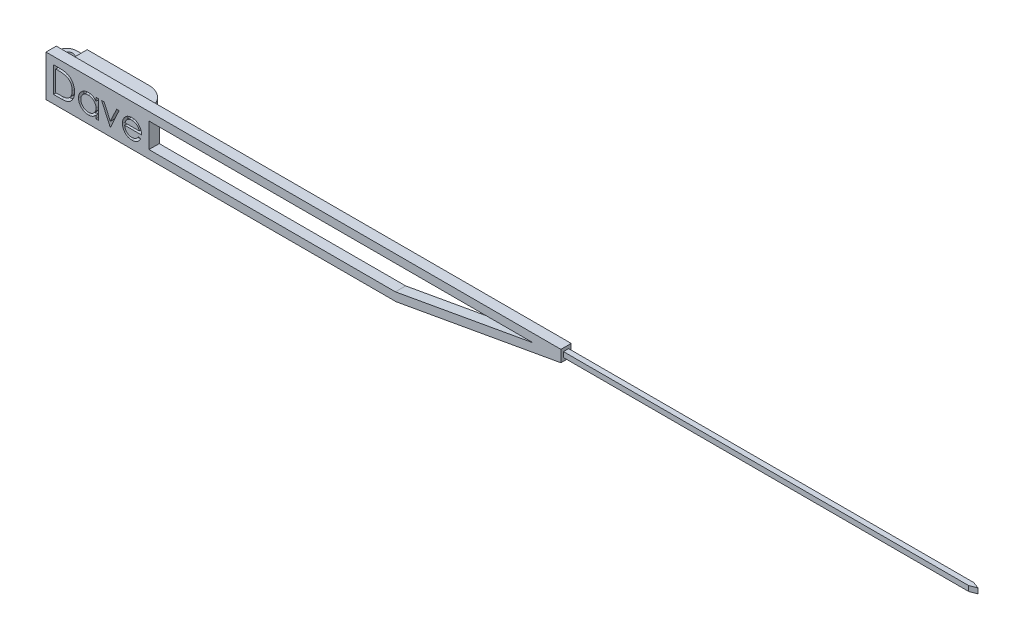
SolidWorks part; units mm, degrees
material "1060 Alloy"
ref_plane "Front" through (0, 0, 0) normal (0, 0, 1) x (1, 0, 0)
ref_plane "Top" through (0, 0, 0) normal (0, 1, 0) x (1, 0, 0)
ref_plane "Right" through (0, 0, 0) normal (1, 0, 0) x (0, 0, -1)
sketch "Sketch1" plane through (0, 0, 0) normal (0, 0, 1) x (1, 0, 0)
  line L0 (0, -2.54) -> (0, 2.54)
  line L1 (0, 2.54) -> (63.5, 2.54)
  line L2 (63.5, 2.54) -> (63.5, 1.101)
  line L3 (63.5, 1.101) -> (43.18, -2.54)
  line L4 (43.18, -2.54) -> (0, -2.54)
  point P2 (0, 0)
  dimension "D1" = 5.08
  dimension "D2" = 63.5
  dimension "D3" = 43.18
  dimension "D4" = 10.159
extrude "Boss-Extrude1" add sketch "Sketch1" along normal mid plane 1.27
sketch "Sketch3" plane through (0, 0, 0) normal (0, 0, 1) x (1, 0, 0)
  line L0 (63.5, 1.8205) -> (114.3, 1.8205)
  line L2 (63.5, 1.101) -> (63.5, 2.54) construction
  dimension "D2" = 50.8
ref_plane "Plane1" through (63.5, 0, 0) normal (1, 0, 0) x (0, 0, -1)
sketch "Sketch4" plane through (63.5, 0, 0) normal (1, 0, 0) x (0, 0, -1)
  line L0 (-0.635, 2.54) -> (0.635, 1.101) construction
  line L5 (-0.3175, 2.138) -> (0.3175, 1.503) construction
  line L6 (-0.635, 1.101) -> (0.635, 2.54) construction
  line L7 (-0.3175, 1.503) -> (0.3175, 1.503)
  line L8 (-0.3175, 1.503) -> (-0.3175, 2.138)
  line L9 (-0.3175, 2.138) -> (0.3175, 2.138)
  line L10 (0.3175, 1.503) -> (0.3175, 2.138)
  line L11 (-0.3175, 1.503) -> (0.3175, 2.138) construction
  point P8 (0, 1.8205)
  point P9 (0, 1.8205)
  dimension "D1" = 0.635
  dimension "D2" = 0.635
sweep "Sweep1" add profiles "Sketch4" path "Sketch3"
sketch "Sketch5" plane through (0, 0, 0.635) normal (0, 0, 1) x (1, 0, 0)
  line L0 (0, 0) -> (12.7, 0) construction
  line L5 (0, 2.54) -> (0, -2.54) construction
  line L18 (12.7, 1.524) -> (12.7, -1.524)
  line L38 (0, -1.524) -> (43.0897, -1.524)
  line L39 (43.0897, -1.524) -> (60.1004, 1.524)
  line L40 (60.1004, 1.524) -> (0, 1.524)
  line L41 (12.7, -1.524) -> (43.0897, -1.524)
  line L42 (43.0897, -1.524) -> (60.1004, 1.524)
  line L43 (60.1004, 1.524) -> (12.7, 1.524)
  dimension "D1" = 12.7
  dimension "D3" = 1.016
extrude "Cut-Extrude2" cut sketch "Sketch5" against normal through all
ref_plane "Plane2" through (0, 0, -0.635) normal (0, 0, -1) x (-1, 0, 0)
sketch "Sketch7" plane through (0, 0, -0.635) normal (0, 0, -1) x (-1, 0, 0)
  line L0 (-12.7, 1.524) -> (0, 1.524) construction
  line L1 (-11.43, 1.524) -> (-1.27, 1.524)
  line L2 (-11.43, 1.524) -> (-11.43, -1.524)
  line L3 (-11.43, -1.524) -> (-1.27, -1.524)
  line L4 (-1.27, 1.524) -> (-1.27, -1.524)
  line L5 (0, 2.54) -> (0, -2.54) construction
  line L6 (-12.7, -1.524) -> (0, -1.524) construction
  dimension "D1" = 10.16
  dimension "D2" = 1.27
extrude "Boss-Extrude2" add sketch "Sketch7" along normal blind 2.54
fillet "Fillet1" radius 2.54 1 edges at (11.43, 0, -3.175)
ref_plane "Plane4" through (0, 0.127, 0) normal (0, 1, 0) x (1, 0, 0)
sketch "Sketch9" plane through (0, 0.127, 0) normal (0, 1, 0) x (1, 0, 0)
  line L0 (63.5, 0.635) -> (0, 0.635) construction
  line L1 (1.27, 3.175) -> (-1.27, 3.175)
  line L2 (1.27, 3.175) -> (1.27, 0.635)
  line L3 (1.27, 0.635) -> (-1.27, 0.635)
  line L4 (-1.27, 3.175) -> (-1.27, 0.635)
  dimension "D1" = 2.54
extrude "Boss-Extrude3" add sketch "Sketch9" along normal mid plane 1.27
sketch "Sketch10" plane through (0, 0.762, 0) normal (0, 1, 0) x (1, 0, 0)
  line L0 (0, 3.175) -> (-1.27, 3.175)
  line L2 (-1.27, 3.175) -> (-1.27, 0.635)
  line L3 (-1.27, 0.635) -> (0, 0.635)
  arc A0 (0, 3.175) -> (0, 0.635) centre (0, 1.905) ccw
  line M3 (1.27, 3.175) -> (-1.27, 3.175)
  line M4 (-1.27, 3.175) -> (-1.27, 0.635)
  line M5 (-1.27, 0.635) -> (0, 0.635)
extrude "Cut-Extrude3" cut sketch "Sketch10" against normal through all contours A0 M3 M4 | A0 L2 M5 region at (-0.9863, 0.762, -2.8913) region at (-0.9863, 0.762, -0.9187)
sketch "Sketch11" plane through (0, 0.762, 0) normal (0, 1, 0) x (1, 0, 0)
  circle A0 centre (0, 1.905) radius 0.762
  dimension "D1" = 1.524
extrude "Cut-Extrude4" cut sketch "Sketch11" against normal through all
sketch "Sketch12" plane through (0, 0, 0.635) normal (0, 0, 1) x (1, 0, 0)
  line L0 (0, 2.54) -> (0, -2.54) construction
  line L1 (0, -2.54) -> (43.18, -2.54) construction
  text T0 "Dave" font "Century Gothic" height 3.175
  dimension "D1" = 0.508
  dimension "D2" = 1.016
extrude "Cut-Extrude5" cut sketch "Sketch12" against normal blind 0.635
sketch "Sketch14" plane through (0, 2.138, 0) normal (0, 1, 0) x (1, 0, 0)
  line L0 (114.3, 0) -> (113.4696, 0.3175)
  line L1 (63.5, 0) -> (114.3, 0) construction
  line L2 (63.5, 0.3175) -> (114.3, 0.3175) construction
  line L4 (63.5, -0.3175) -> (114.3, -0.3175) construction
  line L5 (113.4696, -0.3175) -> (114.3, 0)
  line L6 (114.3, 0.3175) -> (114.3, -0.3175) construction
  line L7 (113.4696, -0.3175) -> (114.3, -0.3175)
  line L8 (114.3, -0.3175) -> (114.3, 0.3175)
  line L9 (114.3, 0.3175) -> (113.4696, 0.3175)
  line M4 (63.5, -0.3175) -> (114.3, -0.3175)
  line M5 (114.3, -0.3175) -> (114.3, 0.3175)
  line M6 (114.3, 0.3175) -> (63.5, 0.3175)
  dimension "D1" = 0.889
extrude "Cut-Extrude7" cut sketch "Sketch14" against normal blind 55.88 contours L5 M4 M5 | L0 M5 M6 region at (114.0232, 2.138, 0.2117) region at (114.0232, 2.138, -0.2117)
ref_plane "Plane5" through (0, 0, -1.905) normal (0, 0, -1) x (-1, 0, 0)
